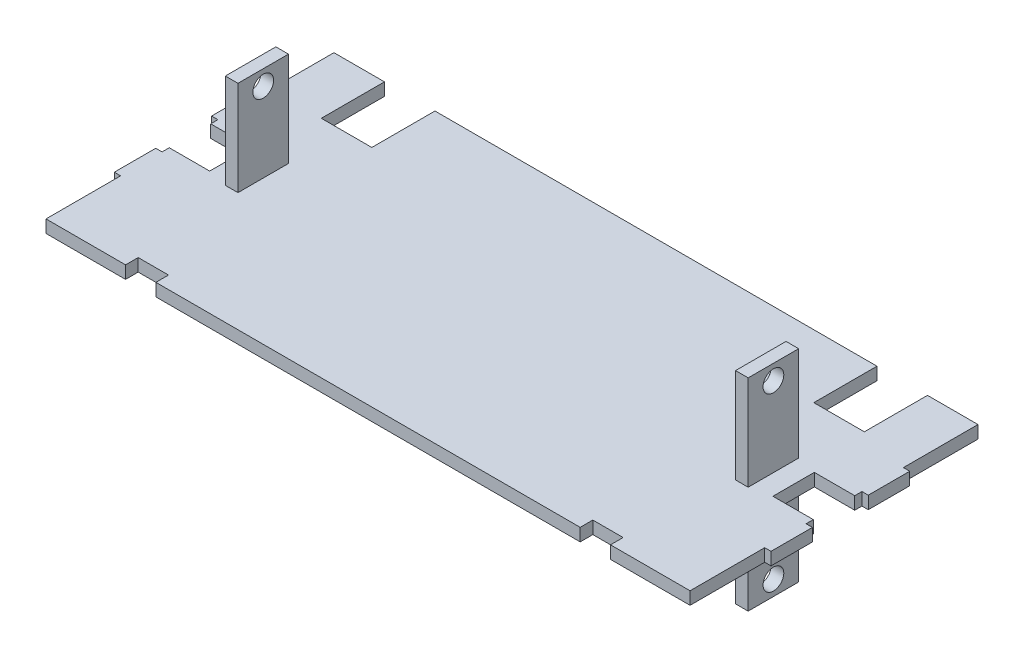
SolidWorks part; units mm, degrees
ref_plane "Front Plane" through (0, 0, 0) normal (0, 0, 1) x (1, 0, 0)
ref_plane "Top Plane" through (0, 0, 0) normal (0, 1, 0) x (1, 0, 0)
ref_plane "Right Plane" through (0, 0, 0) normal (1, 0, 0) x (0, 0, -1)
sketch "Sketch1" plane through (0, 0, 0) normal (0, 1, 0) x (1, 0, 0)
  line L0 (0, 72.39) -> (0, -72.39) construction
  line L1 (161.925, -72.39) -> (121.92, -72.39)
  line L2 (161.925, -72.39) -> (161.925, -34.8747)
  line L3 (161.925, 72.39) -> (136.525, 72.39)
  line L4 (-161.925, -72.39) -> (-161.925, -34.8747)
  line L5 (161.925, -72.39) -> (-161.925, 72.39) construction
  line L6 (161.925, 72.39) -> (-161.925, -72.39) construction
  line L7 (161.925, 10.414) -> (141.605, 10.414)
  line L9 (161.925, -10.414) -> (141.605, -10.414)
  line L10 (141.605, 10.414) -> (141.605, -10.414)
  line L11 (-136.525, 72.39) -> (-161.925, 72.39)
  line L13 (-161.925, -10.414) -> (-141.605, -10.414)
  line L14 (-141.605, 10.414) -> (-141.605, -10.414)
  line L15 (-161.925, 10.414) -> (-141.605, 10.414)
  line L17 (-127, 0) -> (127, 0) construction
  line L18 (-161.925, 14.0467) -> (-165.1, 14.0467)
  line L20 (-161.925, 34.8747) -> (-165.1, 34.8747)
  line L21 (-165.1, 14.0467) -> (-165.1, 34.8747)
  line L22 (-161.925, -34.8747) -> (-165.1, -34.8747)
  line L23 (-165.1, -14.0467) -> (-165.1, -34.8747)
  line L24 (-161.925, -14.0467) -> (-165.1, -14.0467)
  line L27 (161.925, -14.0467) -> (165.1, -14.0467)
  line L28 (165.1, -14.0467) -> (165.1, -34.8747)
  line L29 (161.925, -34.8747) -> (165.1, -34.8747)
  line L30 (161.925, 34.8747) -> (165.1, 34.8747)
  line L31 (165.1, 14.0467) -> (165.1, 34.8747)
  line L32 (161.925, 14.0467) -> (165.1, 14.0467)
  line L34 (-161.925, 34.8747) -> (-161.925, 72.39)
  line L35 (-161.925, -14.0467) -> (-161.925, -10.414)
  line L36 (161.925, 34.8747) -> (161.925, 72.39)
  line L37 (161.925, -14.0467) -> (161.925, -10.414)
  line L38 (-161.925, 10.414) -> (-161.925, 14.0467)
  line L39 (161.925, 10.414) -> (161.925, 14.0467)
  line L40 (-136.525, 72.39) -> (-136.525, 40.64)
  line L41 (-136.525, 40.64) -> (-111.125, 40.64)
  line L42 (-111.125, 72.39) -> (-111.125, 40.64)
  line L44 (111.125, 72.39) -> (111.125, 40.64)
  line L45 (111.125, 40.64) -> (136.525, 40.64)
  line L46 (136.525, 72.39) -> (136.525, 40.64)
  line L47 (111.125, 72.39) -> (-111.125, 72.39)
  line L48 (106.68, -72.39) -> (-106.68, -72.39)
  line L50 (106.68, -72.39) -> (106.68, -66.04)
  line L51 (106.68, -66.04) -> (121.92, -66.04)
  line L52 (121.92, -72.39) -> (121.92, -66.04)
  line L53 (-121.92, -72.39) -> (-121.92, -66.04)
  line L54 (-106.68, -66.04) -> (-121.92, -66.04)
  line L55 (-106.68, -72.39) -> (-106.68, -66.04)
  line L56 (-121.92, -72.39) -> (-161.925, -72.39)
  point P0 (0, 0)
  point P6 (127, 0)
  point P47 (121.92, -69.215)
  dimension "D1" = 323.85
  dimension "D2" = 144.78
  dimension "D3" = 20.828
  dimension "D5" = 3.175
  dimension "D6" = 20.828
  dimension "D4" = 20.32
  dimension "D7" = 31.75
  dimension "D8" = 25.4
  dimension "D9" = 25.4
  dimension "D10" = 31.75
  dimension "D12" = 25.4
  dimension "D11" = 25.4
  dimension "D13" = 15.24
  dimension "D14" = 6.35
  dimension "D15" = 40.005
extrude "Boss-Extrude1" add sketch "Sketch1" along normal mid plane 6.35
sketch "Sketch2" plane through (0, 0, 0) normal (0, 1, 0) x (1, 0, 0)
  line L0 (-141.605, 10.414) -> (-141.605, -10.414) construction
  line L1 (125.095, -12.7) -> (131.445, -12.7)
  line L2 (125.095, -12.7) -> (125.095, 12.7)
  line L3 (125.095, 12.7) -> (131.445, 12.7)
  line L4 (131.445, -12.7) -> (131.445, 12.7)
  line L5 (125.095, -12.7) -> (131.445, 12.7) construction
  line L6 (125.095, 12.7) -> (131.445, -12.7) construction
  line L9 (-125.095, -12.7) -> (-125.095, 12.7)
  line L10 (-125.095, 12.7) -> (-131.445, 12.7)
  line L11 (-131.445, -12.7) -> (-131.445, 12.7)
  line L12 (-125.095, -12.7) -> (-131.445, -12.7)
  line L13 (141.605, -10.414) -> (141.605, 10.414) construction
  point P0 (128.27, 0)
  point P10 (141.605, 0)
  dimension "D1" = 10.16
  dimension "D2" = 10.16
  dimension "D3" = 25.4
  dimension "D4" = 25.4
  dimension "D5" = 6.35
  dimension "D6" = 6.35
  dimension "D7" = 6.35
extrude "Boss-Extrude2" add sketch "Sketch2" along normal mid plane 101.6
sketch "Sketch3" plane through (-131.445, 0, 0) normal (-1, 0, 0) x (0, 0, 1)
  line L0 (-12.7, 50.8) -> (12.7, 50.8) construction
  line L1 (-12.7, -50.8) -> (12.7, -50.8) construction
  circle A0 centre (0, 43.18) radius 5.207
  circle A1 centre (0, -43.18) radius 5.207
  point P4 (0, 50.8)
  dimension "D1" = 10.414
  dimension "D2" = 10.414
  dimension "D3" = 7.62
  dimension "D4" = 7.62
  dimension "D5" = 86.36
extrude "Cut-Extrude1" cut sketch "Sketch3" against normal through all both and the other way through all
equation "\"length\"= 12.75"
equation "\"width\"= 5.7"
equation "\"height\"= 0.25"
equation "\"D1@Sketch1\"=\"length\""
equation "\"D2@Sketch1\"=\"width\""
equation "\"eyebolt width\"= 0.82"
equation "\"eyebolt length\"= 0.8"
equation "\"D3@Sketch1\"=\"eyebolt width\""
equation "\"D4@Sketch1\"=\"eyebolt length\""
equation "\"lead screw holder height\"= 2.76"
equation "\"lead screw diameter\"=0.41"
equation "\"D1@Sketch3\"=\"lead screw diameter\""
equation "\"distance from holders to board\"=0.4"
equation "\"D2@Sketch3\"=\"lead screw diameter\""
equation "\"lead_screw_dist\"=3.4"
equation "\"D5@Sketch3\"=\"lead_screw_dist\""
